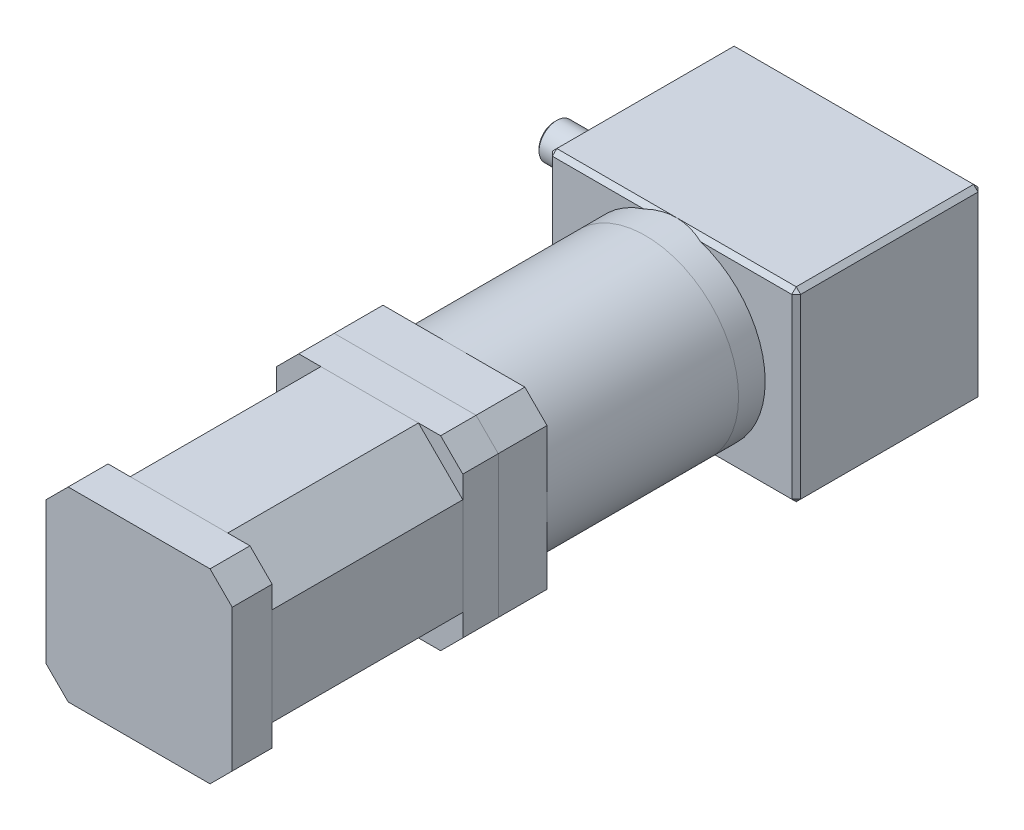
SolidWorks part; units mm, degrees
material "1060 합금"
ref_plane "정면" through (0, 0, 0) normal (0, 0, 1) x (1, 0, 0)
ref_plane "윗면" through (0, 0, 0) normal (0, 1, 0) x (1, 0, 0)
ref_plane "우측면" through (0, 0, 0) normal (1, 0, 0) x (0, 0, -1)
sketch "스케치1" plane through (0, 0, 0) normal (0, 0, 1) x (1, 0, 0)
  line L1 (-21, 21) -> (21, 21)
  line L2 (-21, 21) -> (-21, -21)
  line L3 (-21, -21) -> (21, -21)
  line L4 (21, 21) -> (21, -21)
  line L5 (-21, 21) -> (21, -21) construction
  line L6 (-21, -21) -> (21, 21) construction
  point P0 (0, 0)
  dimension "D1" = 42
  dimension "D2" = 42
extrude "보스-돌출1" add sketch "스케치1" along normal blind 60
ref_plane "평면1" through (0, 0, 51) normal (0, 0, 1) x (1, 0, 0)
ref_plane "평면2" through (0, 0, 8) normal (0, 0, -1) x (-1, 0, 0)
split line "분할선1"
split line "분할선2"
chamfer "모따기1" distance 5 angle 45 12 edges at (-21, -21, 55.5) (-21, -21, 4) (-21, -21, 29.5) (21, -21, 55.5) (21, -21, 4) (21, -21, 29.5) (21, 21, 4) (21, 21, 29.5) (21, 21, 55.5) (-21, 21, 4) (-21, 21, 29.5) (-21, 21, 55.5)
sketch "스케치2" plane through (0, 0, 51) normal (0, 0, 1) x (1, 0, 0)
  line L0 (-11, 21) -> (-21, 21)
  line L3 (16, 21) -> (-16, 21) construction
  line L4 (-21, 21) -> (-21, 11)
  line L5 (-21, 16) -> (-21, -16) construction
  line L6 (-11, 21) -> (-21, 11)
  line L7 (-16, 21) -> (-21, 16) construction
  line L8 (21, 11) -> (21, 21)
  line L9 (21, 21) -> (11, 21)
  line L10 (21, 11) -> (11, 21)
  line L11 (11, -21) -> (21, -21)
  line L12 (21, -21) -> (21, -11)
  line L13 (11, -21) -> (21, -11)
  line L14 (-21, -11) -> (-21, -21)
  line L15 (-21, -21) -> (-11, -21)
  line L16 (-21, -11) -> (-11, -21)
  point P21 (0, 0)
  dimension "D1" = 10
  dimension "D2" = 4
extrude "컷-돌출1" cut sketch "스케치2" against normal up to vertex (43 mm away) up to point (-21, 16, 8)
ref_plane "평면3" through (0, 0, 0) normal (0, 0, -1) x (-1, 0, 0)
sketch "스케치3" plane through (0, 0, 0) normal (0, 0, -1) x (-1, 0, 0)
  line L0 (-16, 21) -> (-21, 16)
  line L1 (-21, 16) -> (-21, -16)
  line L2 (-21, -16) -> (-16, -21) construction
  line L3 (-21, -16) -> (-16, -21)
  line L4 (-16, -21) -> (16, -21)
  line L5 (16, -21) -> (21, -16)
  line L6 (21, -16) -> (21, 16)
  line L7 (21, 16) -> (16, 21)
  line L8 (16, 21) -> (-16, 21)
extrude "보스-돌출2" add sketch "스케치3" along normal blind 11
split line "분할선3"
sketch "스케치4" plane through (0, 0, -11) normal (0, 0, -1) x (-1, 0, 0)
  circle A0 centre (0, 0) radius 21
  dimension "D1" = 42
extrude "보스-돌출3" add sketch "스케치4" along normal blind 49.2
ref_plane "평면4" through (0, 0, -54.2) normal (0, 0, -1) x (-1, 0, 0)
split line "분할선4"
sketch "스케치5" plane through (0, 0, -60.2) normal (0, 0, -1) x (-1, 0, 0)
  line L1 (-28, 21) -> (28, 21)
  line L2 (-28, 21) -> (-28, -21)
  line L3 (-28, -21) -> (28, -21)
  line L4 (28, 21) -> (28, -21)
  line L5 (-28, 21) -> (28, -21) construction
  line L6 (-28, -21) -> (28, 21) construction
  point P0 (0, 0)
  point P5 (0, 0)
  dimension "D1" = 42
  dimension "D2" = 56
extrude "보스-돌출4" add sketch "스케치5" along normal blind 42
chamfer "모따기2" distance 1 angle 45 14 edges at (28, 0, -60.2) (28, -21, -81.2) (14, -21, -60.2) (-14, -21, -60.2) (-28, -21, -81.2) (-28, 0, -60.2) (-28, 21, -81.2) (-14, 21, -60.2) (14, 21, -60.2) (28, 21, -81.2) (0, -21, -102.2) (28, 0, -102.2) (0, 21, -102.2) (-28, 0, -102.2)
sketch "스케치6" plane through (-28, 0, 0) normal (-1, 0, 0) x (0, 0, 1)
  line L0 (-101.2, 20) -> (-101.2, -20) construction
  line L1 (-61.2, -21) -> (-101.2, -21) construction
  circle A0 centre (-83.7, 0) radius 17.5 construction
  dimension "D1" = 35
  dimension "D2" = 21
hole_wizard "M4 나사 구멍1" positions "스케치7" profile "스케치9" tap size "M4" standard "KS"
sketch "스케치7" plane through (-28, 0, 0) normal (-1, 0, 0) x (0, 0, 1)
  line L1 (-83.7, 17.5) -> (-83.7, -17.5) construction
  line L3 (-101.2, 0) -> (-66.2, 0) construction
  line L4 (-96.0744, -12.3744) -> (-83.7, 0) construction
  circle A0 centre (-83.7, 0) radius 17.5 construction
  point P0 (-96.0744, 12.3744)
  point P4 (-71.3256, 12.3744)
  point P6 (-71.3256, -12.3744)
  point P8 (-96.0744, -12.3744)
  dimension "D1" = 45
sketch "스케치9" plane through (-28, 12.3744, -96.0744) normal (0, 1, 0) x (0, 0, 1)
  line L0 (0, 0) -> (0, 11.0914)
  line L1 (0, 11.0914) -> (1.65, 10.1)
  line L2 (1.65, 10.1) -> (1.65, 0)
  line L5 (1.65, 0) -> (0, 0)
  line L10 (0, 11.0914) -> (-1.65, 10.1) construction
  line L11 (0, -6.35) -> (0, 107.95) construction
  dimension "탭 드릴 지름" = 3.3
  dimension "탭 드릴 깊이" = 10.1
  dimension "드릴 각도" = 118
cosmetic thread "구멍 나사산1" parameters "D1"=8, "D2"=4
cosmetic thread "구멍 나사산2" parameters "D1"=8, "D2"=4
cosmetic thread "구멍 나사산3" parameters "D1"=8, "D2"=4
cosmetic thread "구멍 나사산4" parameters "D1"=8, "D2"=4
sketch "스케치10" plane through (-28, 0, 0) normal (-1, 0, 0) x (0, 0, 1)
  circle A0 centre (-83.7, 0) radius 11
  dimension "D1" = 22
extrude "보스-돌출5" add sketch "스케치10" along normal blind 2
sketch "스케치11" plane through (-30, 0, 0) normal (-1, 0, 0) x (0, 0, 1)
  circle A0 centre (-83.7, 0) radius 4
  dimension "D1" = 8
extrude "보스-돌출6" add sketch "스케치11" along normal blind 20
chamfer "모따기3" distance 0.5 angle 45 1 edges at (-50, -4, -83.7)
ref_plane "평면5" through (0, 0, -87.7) normal (0, 0, -1) x (-1, 0, 0)
sketch "스케치12" plane through (0, 0, -87.7) normal (0, 0, -1) x (-1, 0, 0)
  line L0 (37.5, 0) -> (44.5, 0) construction
  line L1 (37.5, 2) -> (44.5, 2)
  line L2 (37.5, -2) -> (44.5, -2)
  line L4 (49.5, -4) -> (49.5, 4) construction
  arc A0 (37.5, 2) -> (37.5, -2) centre (37.5, 0) ccw
  arc A1 (44.5, -2) -> (44.5, 2) centre (44.5, 0) ccw
  point P3 (41, 0)
  point P10 (49.5, -0.546)
  dimension "D3" = 2
  dimension "D1" = 7
  dimension "D2" = 5
extrude "보스-돌출7" add sketch "스케치12" along normal blind 1.2 and the other way blind 1
